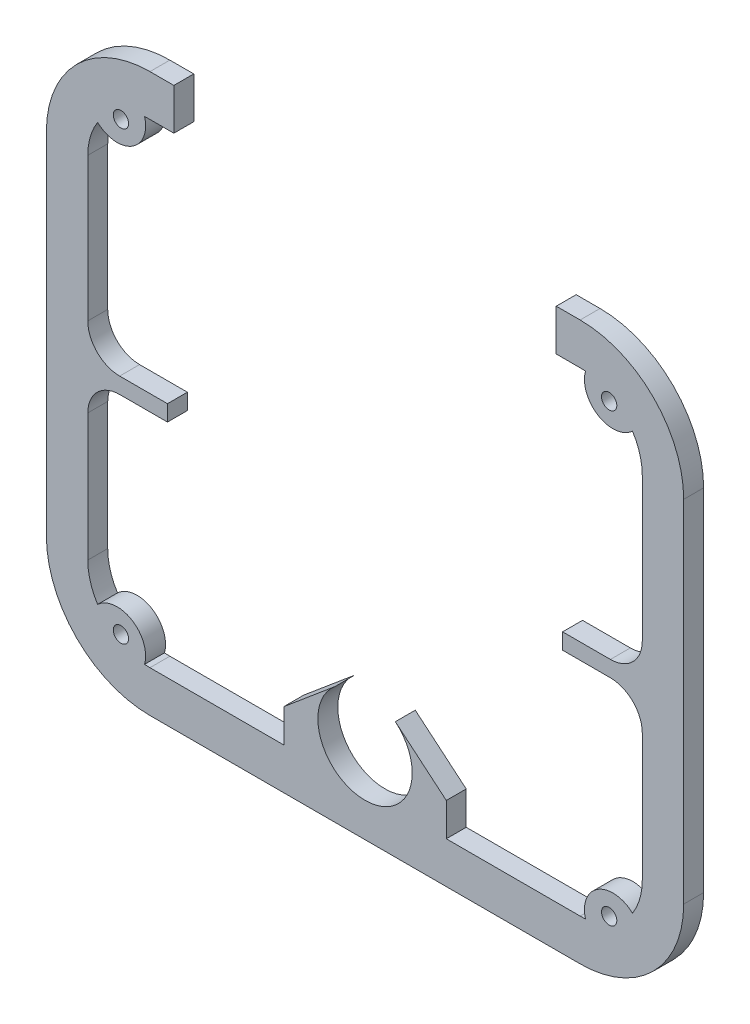
SolidWorks part; units mm, degrees
material "Delrin 2700 NC010, Low Viscosity Acetal Copolymer (SS)"
ref_plane "Front Plane" through (0, 0, 0) normal (0, 0, 1) x (1, 0, 0)
ref_plane "Top Plane" through (0, 0, 0) normal (0, 1, 0) x (1, 0, 0)
ref_plane "Right Plane" through (0, 0, 0) normal (1, 0, 0) x (0, 0, -1)
sketch "Sketch1" plane through (0, 0, 0) normal (0, 0, 1) x (1, 0, 0)
  line L0 (-17.145, -18.923) -> (-9.6321, -18.923)
  line L1 (17.145, 22.225) -> (-17.145, 22.225)
  line L2 (25.4, 13.97) -> (25.4, -13.97)
  line L3 (17.145, -22.225) -> (-17.145, -22.225)
  line L4 (-25.4, 13.97) -> (-25.4, -13.97)
  line L5 (25.4, 22.225) -> (-25.4, -22.225) construction
  line L6 (25.4, -22.225) -> (-25.4, 22.225) construction
  line L7 (9.6321, -18.923) -> (17.145, -18.923)
  line L8 (15.748, 0) -> (15.748, -1.27)
  line L9 (-22.098, 0) -> (-15.748, 0)
  line L10 (-22.098, 13.97) -> (-22.098, -13.97)
  line L11 (-1000, 0) -> (49000, 0) construction
  line L12 (-22.098, 0) -> (-22.098, -1.27)
  line L13 (22.098, 13.97) -> (22.098, -13.97)
  line L14 (17.145, 18.923) -> (-17.145, 18.923)
  line L15 (-22.098, -1.27) -> (-15.748, -1.27)
  line L16 (-15.748, 0) -> (-15.748, -1.27)
  line L17 (22.098, 0) -> (15.748, 0)
  line L18 (0, 18.923) -> (0, -18.415) construction
  line L19 (22.098, -1.27) -> (15.748, -1.27)
  line L21 (2.4164, -12.8683) -> (9.6321, -18.923)
  line L22 (-2.4164, -12.8683) -> (-9.6321, -18.923)
  line L36 (17.145, -18.923) -> (-17.145, -18.923) construction
  arc A0 (-2.4164, -12.8683) -> (2.4164, -12.8683) centre (0, -15.748) ccw
  arc A1 (-17.145, 22.225) -> (-25.4, 13.97) centre (-17.145, 13.97) ccw
  arc A2 (17.145, 22.225) -> (25.4, 13.97) centre (17.145, 13.97) cw
  arc A3 (25.4, -13.97) -> (17.145, -22.225) centre (17.145, -13.97) cw
  arc A4 (-17.145, -22.225) -> (-25.4, -13.97) centre (-17.145, -13.97) cw
  arc A5 (-21.3168, 16.6398) -> (-17.5714, 18.9046) centre (-19.7605, 18.2953) ccw
  arc A6 (21.3168, 16.6398) -> (17.5714, 18.9046) centre (19.7605, 18.2953) cw
  arc A7 (17.145, 18.923) -> (22.098, 13.97) centre (17.145, 13.97) cw
  arc A8 (-17.145, 18.923) -> (-22.098, 13.97) centre (-17.145, 13.97) ccw
  circle A9 centre (-19.4575, 17.78) radius 0.6096
  circle A10 centre (19.4575, 17.78) radius 0.6096
  circle A11 centre (-19.4575, -17.78) radius 0.6096
  circle A12 centre (19.4575, -17.78) radius 0.6096
  arc A13 (-17.145, -18.923) -> (-22.098, -13.97) centre (-17.145, -13.97) cw construction
  arc A14 (22.098, -13.97) -> (17.145, -18.923) centre (17.145, -13.97) cw construction
  arc A15 (-22.098, -13.97) -> (-17.145, -18.923) centre (-17.145, -13.97) ccw
  arc A16 (17.145, -18.923) -> (22.098, -13.97) centre (17.145, -13.97) ccw
  arc A17 (21.3168, -16.6398) -> (17.5714, -18.9046) centre (19.7605, -18.2953) ccw
  arc A18 (-21.3168, -16.6398) -> (-17.5714, -18.9046) centre (-19.7605, -18.2953) cw
  point P0 (0, 0)
  dimension "D4" = 7.5184
  dimension "D6" = 8.255
  dimension "D7" = 8.255
  dimension "D8" = 8.255
  dimension "D9" = 8.255
  dimension "D5" = 1.2192
  dimension "D1" = 50.8
  dimension "D2" = 44.45
  dimension "D10" = 3.302
  dimension "D3" = 3.175
  dimension "D11" = 17.78
  dimension "D12" = 19.4575
  dimension "D13" = 15.748
  dimension "D14" = 1.27
  dimension "D15" = 6.35
extrude "Boss-Extrude1" add sketch "Sketch1" along normal blind 1.5875 contours A4 L3 A3 L2 A2 L1 A1 L4 A16 L7 L21 A0 L22 L0 A15 A11 L10 A8 A9 L14 A7 A10 L13 A12 | A9 A8 A5 | A16 A17 A12 | A18 A15 A11 | A7 A10 A6 | L16 L9 L10 L15 | L19 L13 L17 L8 region at (-18.4919, -18.6865, 0) region at (-18.923, -0.635, 0) region at (18.6095, -16.3919, 0) region at (-20.7018, 17.3477, 0) region at (18.923, -0.635, 0) region at (18.4919, 18.6865, 0) region at (22.5049, 19.3299, 0)
sketch "Sketch2" plane through (0, 0, 1.5875) normal (0, 0, 1) x (1, 0, 0)
  line L1 (-9.6321, -18.923) -> (-6.477, -18.923)
  line L2 (-9.6321, -18.923) -> (-9.6321, -16.2756)
  line L3 (-9.6321, -16.2756) -> (-6.477, -16.2756)
  line L4 (-6.477, -18.923) -> (-6.477, -16.2756)
  line L5 (0, -1000) -> (0, 49000) construction
  line L6 (9.6321, -18.923) -> (9.6321, -16.2756)
  line L7 (9.6321, -16.2756) -> (6.477, -16.2756)
  line L8 (6.477, -18.923) -> (6.477, -16.2756)
  line L9 (9.6321, -18.923) -> (6.477, -18.923)
  line L11 (-15.24, 18.923) -> (15.24, 18.923)
  line L12 (-15.24, 18.923) -> (-15.24, 22.225)
  line L13 (-15.24, 22.225) -> (15.24, 22.225)
  line L14 (15.24, 18.923) -> (15.24, 22.225)
  line L16 (17.145, 18.923) -> (-17.145, 18.923) construction
  line L17 (-2.4164, -12.8683) -> (-9.6321, -18.923) construction
  line L18 (17.145, 22.225) -> (-17.145, 22.225) construction
  point P25 (0, 22.225)
  dimension "D1" = 6.477
  dimension "D2" = 30.48
extrude "Cut-Extrude1" cut sketch "Sketch2" against normal up to next
fillet "Fillet1" radius 2.54 4 edges at (22.098, -1.27, 0.7937) (22.098, 0, 0.7937) (-22.098, 0, 0.7937) (-22.098, -1.27, 0.7937)
